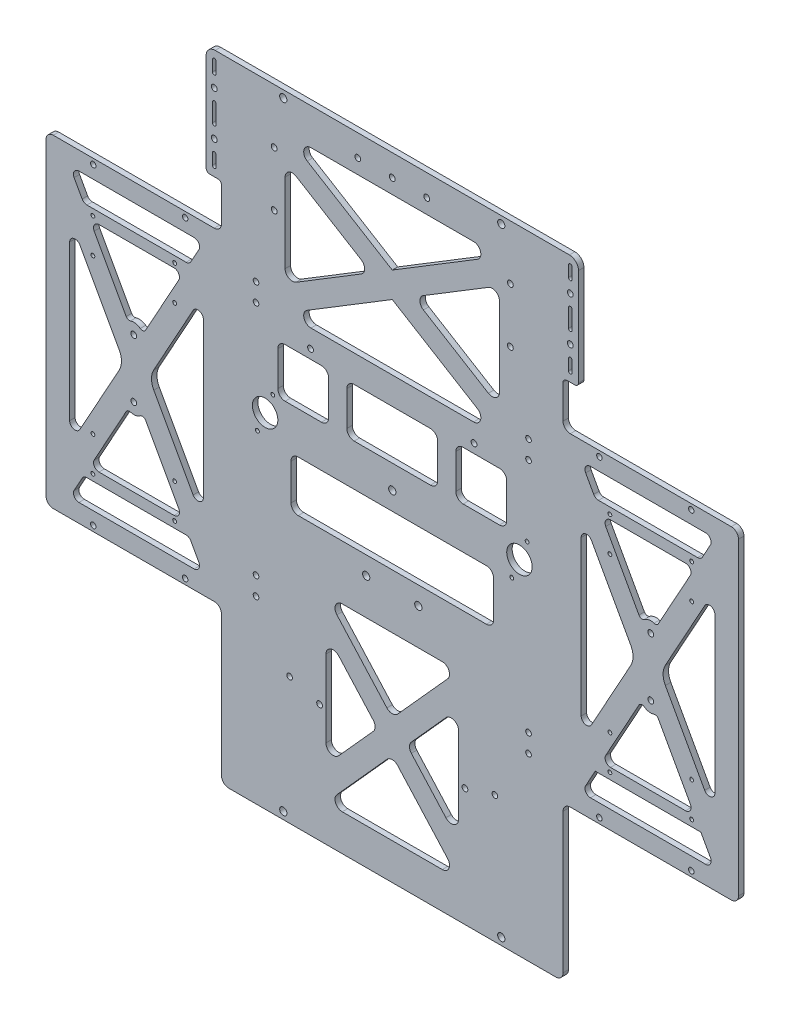
SolidWorks part; units mm, degrees
material "Thornel Mat VMA"
ref_plane "前视基准面" through (0, 0, 0) normal (0, 0, 1) x (1, 0, 0)
ref_plane "上视基准面" through (0, 0, 0) normal (0, 1, 0) x (1, 0, 0)
ref_plane "右视基准面" through (0, 0, 0) normal (1, 0, 0) x (0, 0, -1)
sketch "草图1" plane through (0, 0, 0) normal (0, 0, 1) x (1, 0, 0)
  line L0 (0, 218.8611) -> (0, -216.7734) construction
  line L1 (-286.7115, 0) -> (319.4189, 0) construction
  line L2 (-94, -89) -> (-94, -174)
  line L3 (-94, 174) -> (94, 174)
  line L4 (-94, 174) -> (-94, 89)
  line L5 (-94, -174) -> (94, -174)
  line L6 (94, 174) -> (94, 89)
  line L7 (-94, 174) -> (94, -174) construction
  line L8 (-94, -174) -> (94, 174) construction
  line L9 (-190.6, 89) -> (-94, 89)
  line L10 (-190.6, 89) -> (-190.6, -89)
  line L11 (-190.6, -89) -> (-94, -89)
  line L13 (190.6, 89) -> (94, 89)
  line L14 (190.6, 89) -> (190.6, -89)
  line L15 (190.6, -89) -> (94, -89)
  line L17 (94, -89) -> (94, -174)
  point P5 (0, 0)
  dimension "D1" = 381.2
  dimension "D2" = 188
  dimension "D3" = 178
  dimension "D4" = 348
extrude "凸台-拉伸1" add sketch "草图1" along normal blind 3
sketch "草图2" plane through (0, 0, 3) normal (0, 0, 1) x (1, 0, 0)
  line L0 (0, 167.8944) -> (0, -170.5969) construction
  line L1 (-236.471, 0) -> (218.9046, 0) construction
  line L2 (-190.6, 89) -> (-190.6, -89) construction
  line L3 (190.6, -89) -> (190.6, 89) construction
  line L4 (-177.6, -79) -> (-104, -79)
  line L5 (-177.6, -79) -> (-177.6, 79)
  line L6 (-177.6, 79) -> (-104, 79)
  line L7 (-104, -79) -> (-104, 79)
  line L8 (-177.6, -79) -> (-104, 79) construction
  line L9 (-177.6, 79) -> (-104, -79) construction
  line L10 (104, -79) -> (177.6, -79)
  line L11 (104, -79) -> (104, 79)
  line L12 (104, 79) -> (177.6, 79)
  line L13 (177.6, -79) -> (177.6, 79)
  line L14 (104, -79) -> (177.6, 79) construction
  line L15 (104, 79) -> (177.6, -79) construction
  line L16 (190.6, 89) -> (94, 89) construction
  line L17 (94, 89) -> (94, 174) construction
  circle A0 centre (164.6, 86) radius 1.5
  circle A1 centre (164.6, -86) radius 1.5
  circle A2 centre (-60, -170) radius 1.5
  circle A3 centre (60, -170) radius 1.5
  circle A4 centre (-164.6, -86) radius 1.5
  circle A5 centre (-164.6, 86) radius 1.5
  circle A6 centre (-60, 170) radius 1.5
  circle A7 centre (60, 170) radius 1.5
  circle A8 centre (-114, 86) radius 1.5
  circle A9 centre (-114, -86) radius 1.5
  circle A10 centre (114, 86) radius 1.5
  circle A11 centre (114, -86) radius 1.5
  point P29 (140.8, 0)
  point P33 (-140.8, 0)
  dimension "D1" = 3
  dimension "D2" = 120
  dimension "D3" = 50.6
  dimension "D4" = 172
  dimension "D5" = 26
  dimension "D6" = 340
  dimension "D7" = 13
  dimension "D8" = 10
  dimension "D9" = 10
extrude "切除-拉伸1" cut sketch "草图2" against normal through all
sketch "草图3" plane through (0, 0, 3) normal (0, 0, 1) x (1, 0, 0)
  line L0 (-177.6, 79) -> (-169.8636, 65)
  line L1 (-104, -79) -> (-104, 79) construction
  line L2 (-104, -54.1893) -> (-104, -79)
  line L3 (-104, -79) -> (-111.7364, -65)
  line L4 (-177.6, 79) -> (-177.6, -79) construction
  line L5 (-177.6, 54.1893) -> (-177.6, 79)
  line L6 (-104, 79) -> (-111.7364, 65)
  line L7 (-177.6, -54.1893) -> (-177.6, -79)
  line L8 (-177.6, -79) -> (-169.8636, -65)
  line L9 (-104, 54.1893) -> (-104, 79)
  line L11 (-104, 79) -> (-177.6, 79) construction
  line L14 (-169.8636, 65) -> (-111.7364, 65)
  line L20 (-133.9449, 0) -> (-104, -54.1893)
  line L21 (-147.6551, 0) -> (-177.6, -54.1893)
  line L22 (-147.6551, 0) -> (-177.6, 54.1893)
  line L23 (-133.9449, 0) -> (-104, 54.1893)
  line L28 (-142.3, 12.0792) -> (-142.3, -12.0792) construction
  line L33 (-166.5481, 59) -> (-115.0519, 59)
  line L34 (-164.8, 30) -> (-119.8, 30) construction
  line L35 (-147.6551, 0) -> (-133.9449, 0) construction
  line L36 (-164.8, 30) -> (-164.8, -30) construction
  line L37 (-164.8, -30) -> (-119.8, -30) construction
  line L38 (-119.8, 30) -> (-119.8, -30) construction
  line L39 (-164.8, 30) -> (-119.8, -30) construction
  line L40 (-164.8, -30) -> (-119.8, 30) construction
  line L41 (-166.8, 65) -> (-117.8, 65) construction
  line L42 (-166.8, 65) -> (-166.8, 39) construction
  line L43 (-166.8, 39) -> (-117.8, 39) construction
  line L44 (-117.8, 65) -> (-117.8, 39) construction
  line L45 (-166.8, 65) -> (-117.8, 39) construction
  line L46 (-166.8, 39) -> (-117.8, 65) construction
  line L47 (-164.8, 61.5) -> (-119.8, 61.5) construction
  line L48 (-164.8, 61.5) -> (-164.8, 42.5) construction
  line L49 (-164.8, 42.5) -> (-119.8, 42.5) construction
  line L50 (-119.8, 61.5) -> (-119.8, 42.5) construction
  line L51 (-164.8, 61.5) -> (-119.8, 42.5) construction
  line L52 (-164.8, 42.5) -> (-119.8, 61.5) construction
  line L53 (-115.0519, 59) -> (-137.1305, 19.0457)
  line L54 (-166.5481, 59) -> (-145.5673, 21.0324)
  line L55 (-166.5481, -59) -> (-115.0519, -59)
  line L56 (-169.8636, -65) -> (-111.7364, -65)
  line L57 (-115.0519, -59) -> (-137.1305, -19.0457)
  line L58 (-166.5481, -59) -> (-145.5673, -21.0324)
  line L59 (0, 125.1469) -> (0, -125.1469) construction
  line L60 (164.8, 42.5) -> (119.8, 61.5) construction
  line L61 (164.8, 61.5) -> (119.8, 42.5) construction
  line L62 (119.8, 61.5) -> (119.8, 42.5) construction
  line L63 (164.8, 42.5) -> (119.8, 42.5) construction
  line L64 (164.8, 61.5) -> (164.8, 42.5) construction
  line L65 (164.8, 61.5) -> (119.8, 61.5) construction
  line L66 (166.8, 39) -> (117.8, 65) construction
  line L67 (166.8, 65) -> (117.8, 39) construction
  line L68 (117.8, 65) -> (117.8, 39) construction
  line L69 (166.8, 39) -> (117.8, 39) construction
  line L70 (166.8, 65) -> (166.8, 39) construction
  line L71 (166.8, 65) -> (117.8, 65) construction
  line L72 (164.8, -30) -> (119.8, 30) construction
  line L73 (164.8, 30) -> (119.8, -30) construction
  line L74 (119.8, 30) -> (119.8, -30) construction
  line L75 (164.8, -30) -> (119.8, -30) construction
  line L76 (164.8, 30) -> (164.8, -30) construction
  line L77 (147.6551, 0) -> (133.9449, 0) construction
  line L78 (164.8, 30) -> (119.8, 30) construction
  line L79 (142.3, 12.0792) -> (142.3, -12.0792) construction
  line L80 (166.5481, -59) -> (145.5673, -21.0324)
  line L81 (115.0519, -59) -> (137.1305, -19.0457)
  line L82 (169.8636, -65) -> (111.7364, -65)
  line L83 (166.5481, -59) -> (115.0519, -59)
  line L84 (166.5481, 59) -> (145.5673, 21.0324)
  line L85 (115.0519, 59) -> (137.1305, 19.0457)
  line L86 (166.5481, 59) -> (115.0519, 59)
  line L87 (133.9449, 0) -> (104, 54.1893)
  line L88 (147.6551, 0) -> (177.6, 54.1893)
  line L89 (147.6551, 0) -> (177.6, -54.1893)
  line L90 (133.9449, 0) -> (104, -54.1893)
  line L91 (169.8636, 65) -> (111.7364, 65)
  line L92 (104, 54.1893) -> (104, 79)
  line L93 (177.6, -79) -> (169.8636, -65)
  line L94 (177.6, -54.1893) -> (177.6, -79)
  line L95 (104, 79) -> (111.7364, 65)
  line L96 (177.6, 54.1893) -> (177.6, 79)
  line L97 (104, -79) -> (111.7364, -65)
  line L98 (104, -54.1893) -> (104, -79)
  line L99 (177.6, 79) -> (169.8636, 65)
  circle A0 centre (-142.3, 16) radius 1.6
  circle A1 centre (-164.8, 61.5) radius 1.05
  circle A2 centre (-119.8, 61.5) radius 1.05
  circle A3 centre (-119.8, 42.5) radius 1.05
  circle A4 centre (-164.8, 42.5) radius 1.05
  arc A5 (-137.1305, 19.0457) -> (-145.5673, 21.0324) centre (-142.3, 16) ccw
  arc A6 (-137.1305, -19.0457) -> (-145.5673, -21.0324) centre (-142.3, -16) cw
  circle A7 centre (-142.3, -16) radius 1.6
  circle A8 centre (-119.8, -42.5) radius 1.05
  circle A9 centre (-164.8, -42.5) radius 1.05
  circle A10 centre (-119.8, -61.5) radius 1.05
  circle A11 centre (-164.8, -61.5) radius 1.05
  circle A12 centre (164.8, -61.5) radius 1.05
  circle A13 centre (119.8, -61.5) radius 1.05
  circle A14 centre (164.8, -42.5) radius 1.05
  circle A15 centre (119.8, -42.5) radius 1.05
  circle A16 centre (142.3, -16) radius 1.6
  arc A17 (137.1305, -19.0457) -> (145.5673, -21.0324) centre (142.3, -16) ccw
  arc A18 (137.1305, 19.0457) -> (145.5673, 21.0324) centre (142.3, 16) cw
  circle A19 centre (164.8, 42.5) radius 1.05
  circle A20 centre (119.8, 42.5) radius 1.05
  circle A21 centre (119.8, 61.5) radius 1.05
  circle A22 centre (164.8, 61.5) radius 1.05
  circle A23 centre (142.3, 16) radius 1.6
  point P13 (-142.3, 0)
  point P25 (-142.3, 52)
  point P37 (-142.3, 52)
  point P69 (0, 0)
  point P122 (142.3, 52)
  point P123 (142.3, 0)
  dimension "D4" = 3.2
  dimension "D10" = 2.1
  dimension "D12" = 12
  dimension "D1" = 12
  dimension "D2" = 45
  dimension "D3" = 60
  dimension "D5" = 16
  dimension "D6" = 49
  dimension "D7" = 26
  dimension "D8" = 45
  dimension "D9" = 19
  dimension "D11" = 14
  dimension "D13" = 6
extrude "凸台-拉伸2" add sketch "草图3" against normal up to surface (3 mm away) up to face at (-163.1, -86, 0)
fillet "圆角2" radius 4 10 edges at (-94, -174, 1.5) (-94, -89, 1.5) (-190.6, -89, 1.5) (-190.6, 89, 1.5) (-94, 89, 1.5) (94, -174, 1.5) (94, -89, 1.5) (190.6, -89, 1.5) (190.6, 89, 1.5) (94, 89, 1.5)
sketch "草图4" plane through (0, 0, 3) normal (0, 0, 1) x (1, 0, 0)
  circle A0 centre (-60, 170) radius 2
  circle A1 centre (60, 170) radius 2
  circle A2 centre (-60, -170) radius 2
  circle A3 centre (60, -170) radius 2
  dimension "D1" = 4
extrude "切除-拉伸2" cut sketch "草图4" against normal through all
fillet "圆角3" radius 2 8 edges at (-145.5673, 21.0324, 1.5) (-137.1305, 19.0457, 1.5) (-145.5673, -21.0324, 1.5) (-137.1305, -19.0457, 1.5) (145.5673, -21.0324, 1.5) (137.1305, -19.0457, 1.5) (145.5673, 21.0324, 1.5) (137.1305, 19.0457, 1.5)
fillet "圆角4" radius 3 30 edges at (-169.8636, -65, 1.5) (-111.7364, -65, 1.5) (-169.8636, 65, 1.5) (-111.7364, 65, 1.5) (-177.6, -79, 1.5) (-166.5481, -59, 1.5) (-177.6, -54.1893, 1.5) (-177.6, 54.1893, 1.5) (-104, 54.1893, 1.5) (-104, -79, 1.5) (-115.0519, -59, 1.5) (-104, -54.1893, 1.5) (-177.6, 79, 1.5) (-166.5481, 59, 1.5) (-104, 79, 1.5) (-115.0519, 59, 1.5) (104, -54.1893, 1.5) (115.0519, -59, 1.5) (104, -79, 1.5) (166.5481, -59, 1.5) (177.6, -79, 1.5) (177.6, -54.1893, 1.5) (104, 54.1893, 1.5) (177.6, 54.1893, 1.5) (115.0519, 59, 1.5) (166.5481, 59, 1.5) (111.7364, 65, 1.5) (169.8636, 65, 1.5) (177.6, 79, 1.5) (104, 79, 1.5)
fillet "圆角5" radius 10 4 edges at (147.6551, 0, 1.5) (133.9449, 0, 1.5) (-133.9449, 0, 1.5) (-147.6551, 0, 1.5)
sketch "草图19" plane through (0, 0, 0) normal (0, 0, -1) x (-1, 0, 0)
  line L0 (0, 174) -> (0, -174) construction
  line L1 (-94, 174) -> (-102.5, 174)
  line L2 (-94, 174) -> (-94, 113.5)
  line L3 (-94, 113.5) -> (-102.5, 113.5)
  line L4 (-102.5, 174) -> (-102.5, 113.5)
  line L5 (94, 174) -> (102.5, 174)
  line L6 (94, 174) -> (94, 113.5)
  line L7 (94, 113.5) -> (102.5, 113.5)
  line L8 (102.5, 174) -> (102.5, 113.5)
  line L9 (-94, 174) -> (94, 174) construction
  line L10 (90, -174) -> (-90, -174) construction
  point P16 (102.5, 143.75)
  dimension "D1" = 205
  dimension "D2" = 60.5
extrude "凸台-拉伸3" add sketch "草图19" against normal up to surface (3 mm away) up to face at (62, 170, 3)
sketch "草图20" plane through (0, 0, 0) normal (0, 0, -1) x (-1, 0, 0)
  line L0 (0, 174) -> (0, 0) construction
  line L1 (-102.5, 174) -> (102.5, 174) construction
  line L3 (-99, 169) -> (-97, 169)
  line L4 (-99, 169) -> (-99, 163)
  line L5 (-99, 163) -> (-97, 163)
  line L6 (-97, 169) -> (-97, 163)
  line L7 (-99, 148.75) -> (-97, 148.75)
  line L8 (-99, 148.75) -> (-99, 138.75)
  line L9 (-99, 138.75) -> (-97, 138.75)
  line L10 (-97, 148.75) -> (-97, 138.75)
  line L11 (-99, 124.5) -> (-97, 124.5)
  line L12 (-99, 124.5) -> (-99, 118.5)
  line L13 (-99, 118.5) -> (-97, 118.5)
  line L14 (-97, 124.5) -> (-97, 118.5)
  line L15 (-99, 143.75) -> (-82.4627, 143.75) construction
  line L16 (99, 118.5) -> (97, 118.5)
  line L17 (97, 124.5) -> (97, 118.5)
  line L18 (99, 124.5) -> (97, 124.5)
  line L19 (99, 124.5) -> (99, 118.5)
  line L20 (99, 138.75) -> (97, 138.75)
  line L21 (97, 148.75) -> (97, 138.75)
  line L22 (99, 148.75) -> (97, 148.75)
  line L23 (99, 148.75) -> (99, 138.75)
  line L24 (99, 163) -> (97, 163)
  line L25 (97, 169) -> (97, 163)
  line L26 (99, 169) -> (97, 169)
  line L27 (99, 169) -> (99, 163)
  dimension "D1" = 6
  dimension "D2" = 10
  dimension "D3" = 5
  dimension "D4" = 25.25
  dimension "D5" = 198
  dimension "D6" = 2
extrude "切除-拉伸13" cut sketch "草图20" against normal through all
sketch "草图22" plane through (0, 0, 0) normal (0, 0, -1) x (-1, 0, 0)
  line L0 (-99, 143.75) -> (169.7088, 143.75) construction
  line L1 (-99, 148.75) -> (-99, 138.75) construction
  line L2 (-98, 169) -> (-98, 118.5) construction
  line L3 (-97, 169) -> (-99, 169) construction
  line L4 (-99, 118.5) -> (-97, 118.5) construction
  line L5 (0, 174) -> (0, 199.7438) construction
  line L6 (-102.5, 174) -> (102.5, 174) construction
  line L7 (-99, 163) -> (-97, 163) construction
  line L8 (-97, 148.75) -> (-99, 148.75) construction
  line L9 (-99, 138.75) -> (-97, 138.75) construction
  line L10 (-97, 124.5) -> (-99, 124.5) construction
  circle A0 centre (-98, 155.875) radius 1.6
  circle A1 centre (-98, 131.625) radius 1.6
  circle A2 centre (-98, 169) radius 1
  circle A3 centre (-98, 163) radius 1
  circle A4 centre (-98, 148.75) radius 1
  circle A5 centre (-98, 138.75) radius 1
  circle A6 centre (-98, 124.5) radius 1
  circle A7 centre (-98, 118.5) radius 1
  circle A8 centre (98, 169) radius 1
  circle A9 centre (98, 163) radius 1
  circle A10 centre (98, 155.875) radius 1.6
  circle A11 centre (98, 148.75) radius 1
  circle A12 centre (98, 138.75) radius 1
  circle A13 centre (98, 131.625) radius 1.6
  circle A14 centre (98, 124.5) radius 1
  circle A15 centre (98, 118.5) radius 1
  dimension "D1" = 24.25
  dimension "D2" = 3.2
extrude "切除-拉伸14" cut sketch "草图22" against normal through all
sketch "草图23" plane through (0, 0, 0) normal (0, 0, -1) x (-1, 0, 0)
  line L0 (0, 174) -> (0, -174) construction
  line L1 (-102.5, 174) -> (102.5, 174) construction
  line L2 (90, -174) -> (-90, -174) construction
  line L3 (-177.6, 0) -> (190.6, 0) construction
  line L4 (-177.6, -42.5577) -> (-177.6, 42.5577) construction
  line L5 (190.6, 85) -> (190.6, -85) construction
  line L6 (-74.225, 25.685) -> (-65.775, 4.315) construction
  line L7 (65.775, 25.685) -> (74.225, 4.315) construction
  circle A0 centre (-65, 144) radius 1.6
  circle A1 centre (65, 144) radius 1.6
  circle A2 centre (-65, 114) radius 1.6
  circle A3 centre (65, 114) radius 1.6
  circle A4 centre (0, 13) radius 2
  circle A5 centre (-14.35, -34.9) radius 2
  circle A6 centre (14.35, -34.9) radius 2
  circle A7 centre (-74.225, 25.685) radius 1.05
  circle A8 centre (-65.775, 4.315) radius 1.05
  circle A9 centre (65.775, 25.685) radius 1.05
  circle A10 centre (74.225, 4.315) radius 1.05
  circle A13 centre (-45, 58) radius 1.6
  circle A14 centre (45, 58) radius 1.6
  circle A17 centre (-56.5, -104) radius 1.55
  circle A18 centre (56.5, -104) radius 1.55
  circle A19 centre (-70, 15) radius 7
  circle A20 centre (70, 15) radius 7
  point P30 (-70, 15)
  point P32 (70, 15)
  dimension "D1" = 3.2
  dimension "D2" = 30
  dimension "D3" = 130
  dimension "D4" = 30
  dimension "D5" = 28.7
  dimension "D6" = 4
  dimension "D7" = 47.9
  dimension "D8" = 13
  dimension "D9" = 21.37
  dimension "D10" = 2.1
  dimension "D11" = 8.45
  dimension "D12" = 8.45
  dimension "D16" = 3.2
  dimension "D17" = 90
  dimension "D18" = 116
  dimension "D19" = 113
  dimension "D21" = 3.1
  dimension "D22" = 70
  dimension "D26" = 14
  dimension "D13" = 21.37
  dimension "D14" = 140
  dimension "D15" = 15
extrude "切除-拉伸15" cut sketch "草图23" against normal through all
sketch "草图24" plane through (0, 0, 0) normal (0, 0, -1) x (-1, 0, 0)
  line L0 (-190.6, 0) -> (190.6, 0) construction
  line L1 (-190.6, -85) -> (-190.6, 85) construction
  line L2 (190.6, 85) -> (190.6, -85) construction
  line L3 (0, -174) -> (0, 174) construction
  line L4 (90, -174) -> (-90, -174) construction
  line L5 (-102.5, 174) -> (102.5, 174) construction
  line L6 (-104, 42.5577) -> (-104, -42.5577) construction
  circle A0 centre (-75, 75) radius 1.55
  circle A1 centre (-75, 65) radius 1.55
  circle A2 centre (-75, -65) radius 1.55
  circle A3 centre (-75, -75) radius 1.55
  circle A4 centre (75, -65) radius 1.55
  circle A5 centre (75, -75) radius 1.55
  circle A6 centre (75, 75) radius 1.55
  circle A7 centre (75, 65) radius 1.55
  dimension "D1" = 3.1
  dimension "D2" = 10
  dimension "D3" = 10
  dimension "D4" = 29
  dimension "D5" = 130
  dimension "D6" = 65
extrude "切除-拉伸16" cut sketch "草图24" against normal through all
sketch "草图26" plane through (0, 0, 0) normal (0, 0, -1) x (-1, 0, 0)
  line L0 (0, -174) -> (0, 202.1106) construction
  line L1 (90, -174) -> (-90, -174) construction
  line L2 (-102.5, 174) -> (102.5, 174) construction
  line L3 (-59, 154) -> (59, 154)
  line L4 (-59, 154) -> (-59, 68)
  line L5 (-59, 68) -> (59, 68)
  line L6 (59, 154) -> (59, 68)
  line L7 (-59, 154) -> (59, 68) construction
  line L8 (-59, 68) -> (59, 154) construction
  line L9 (-63, 53) -> (63, 53)
  line L10 (-63, 53) -> (-63, 26)
  line L11 (-63, 26) -> (63, 26)
  line L12 (63, 53) -> (63, 26)
  line L13 (-63, 53) -> (63, 26) construction
  line L14 (-63, 26) -> (63, 53) construction
  line L15 (-55.775, 3) -> (55.775, 3)
  line L16 (-55.775, 3) -> (-55.775, -24.9)
  line L17 (-55.775, -24.9) -> (55.775, -24.9)
  line L18 (55.775, 3) -> (55.775, -24.9)
  line L19 (-55.775, 3) -> (55.775, -24.9) construction
  line L20 (-55.775, -24.9) -> (55.775, 3) construction
  line L21 (-94, -170) -> (-94, -93) construction
  line L26 (-74, -85) -> (-61.5, -85) construction
  line L27 (-36.5, -54.9) -> (36.5, -54.9)
  line L32 (-36.5, -54.9) -> (-36.5, -154)
  line L33 (-36.5, -154) -> (36.5, -154)
  line L34 (-74, -85) -> (-74, -149) construction
  line L35 (36.5, -54.9) -> (36.5, -154)
  line L36 (-36.5, -54.9) -> (36.5, -154) construction
  line L37 (-36.5, -154) -> (36.5, -54.9) construction
  line L38 (-74, -149) -> (-61.5, -149) construction
  line L39 (-61.5, -85) -> (-61.5, -149) construction
  line L40 (61.5, -85) -> (74, -85) construction
  line L41 (61.5, -85) -> (61.5, -149) construction
  line L42 (61.5, -149) -> (74, -149) construction
  line L43 (74, -85) -> (74, -149) construction
  circle A0 centre (-65, 114) radius 1.6 construction
  circle A1 centre (-45, 58) radius 1.6 construction
  circle A2 centre (0, 13) radius 2 construction
  circle A3 centre (-14.35, -34.9) radius 2 construction
  circle A4 centre (-65.775, 4.315) radius 1.05 construction
  circle A5 centre (56.5, -104) radius 1.55 construction
  circle A6 centre (-75, 65) radius 1.55 construction
  circle A7 centre (-56.5, -104) radius 1.55 construction
  circle A8 centre (-75, -75) radius 1.55 construction
  circle A10 centre (14.35, -34.9) radius 2 construction
  point P5 (0, 111)
  point P10 (0, 39.5)
  point P15 (0, -10.95)
  point P26 (0, -104.45)
  dimension "D12" = 20
  dimension "D14" = 5
  dimension "D1" = 20
  dimension "D2" = 6
  dimension "D3" = 10
  dimension "D4" = 10
  dimension "D5" = 10
  dimension "D6" = 10
  dimension "D7" = 5
  dimension "D8" = 13
  dimension "D9" = 12
  dimension "D10" = 20
  dimension "D11" = 20
  dimension "D13" = 20
  dimension "D15" = 10
  dimension "D16" = 25
extrude "切除-拉伸17" cut sketch "草图26" against normal through all
sketch "草图27" plane through (0, 0, 0) normal (0, 0, -1) x (-1, 0, 0)
  line L0 (-59, 154) -> (0, 118.0273)
  line L1 (59, 68) -> (59, 154) construction
  line L2 (59, 82.0546) -> (59, 68)
  line L3 (59, 68) -> (0, 103.9727)
  line L4 (-59, 154) -> (-59, 68) construction
  line L5 (-59, 139.9454) -> (-59, 154)
  line L6 (59, 154) -> (0, 118.0273)
  line L7 (-59, 82.0546) -> (-59, 68)
  line L8 (-59, 68) -> (0, 103.9727)
  line L9 (59, 139.9454) -> (59, 154)
  line L10 (-11.5257, 111) -> (-59, 82.0546)
  line L11 (11.5257, 111) -> (59, 82.0546)
  line L12 (11.5257, 111) -> (59, 139.9454)
  line L13 (-11.5257, 111) -> (-59, 139.9454)
  line L14 (0, 0) -> (0, 96.1037) construction
  line L15 (63, 53) -> (-63, 53) construction
  line L16 (-35, 53) -> (-25, 53)
  line L17 (-35, 53) -> (-35, 26)
  line L18 (-35, 26) -> (-25, 26)
  line L19 (-25, 53) -> (-25, 26)
  line L20 (-63, 26) -> (63, 26) construction
  line L21 (-36.5, -54.9) -> (0, -95.4782)
  line L22 (25, 53) -> (35, 53)
  line L23 (25, 53) -> (25, 26)
  line L24 (25, 26) -> (35, 26)
  line L25 (35, 53) -> (35, 26)
  line L26 (36.5, -154) -> (36.5, -54.9) construction
  line L27 (36.5, -136.0563) -> (36.5, -154)
  line L28 (36.5, -154) -> (0, -113.4218)
  line L29 (-36.5, -54.9) -> (-36.5, -154) construction
  line L30 (-36.5, -72.8437) -> (-36.5, -54.9)
  line L31 (36.5, -54.9) -> (0, -95.4782)
  line L32 (-36.5, -136.0563) -> (-36.5, -154)
  line L33 (-36.5, -154) -> (0, -113.4218)
  line L34 (36.5, -72.8437) -> (36.5, -54.9)
  line L35 (8.0702, -104.45) -> (36.5, -72.8437)
  line L36 (8.0702, -104.45) -> (36.5, -136.0563)
  line L37 (-8.0702, -104.45) -> (-36.5, -136.0563)
  line L38 (-8.0702, -104.45) -> (-36.5, -72.8437)
  dimension "D1" = 12
  dimension "D2" = 10
  dimension "D3" = 50
  dimension "D4" = 12
extrude "凸台-拉伸4" add sketch "草图27" against normal up to surface (3 mm away) up to face at (0, 111, 3)
fillet "圆角6" radius 4 38 edges at (55.775, -24.9, 1.5) (55.775, 3, 1.5) (-55.775, -24.9, 1.5) (-55.775, 3, 1.5) (63, 53, 1.5) (63, 26, 1.5) (35, 26, 1.5) (35, 53, 1.5) (25, 53, 1.5) (25, 26, 1.5) (-25, 26, 1.5) (-25, 53, 1.5) (-35, 53, 1.5) (-35, 26, 1.5) (-63, 26, 1.5) (-63, 53, 1.5) (-59, 68, 1.5) (59, 68, 1.5) (59, 82.0546, 1.5) (-11.5257, 111, 1.5) (11.5257, 111, 1.5) (59, 139.9454, 1.5) (59, 154, 1.5) (-59, 154, 1.5) (-59, 139.9454, 1.5) (-59, 82.0546, 1.5) (36.5, -154, 1.5) (36.5, -136.0563, 1.5) (36.5, -72.8437, 1.5) (8.0702, -104.45, 1.5) (0, -113.4218, 1.5) (-36.5, -154, 1.5) (-36.5, -136.0563, 1.5) (-36.5, -72.8437, 1.5) (-8.0702, -104.45, 1.5) (0, -95.4782, 1.5) (-36.5, -54.9, 1.5) (36.5, -54.9, 1.5)
fillet "圆角7" radius 2 4 edges at (94, 113.5, 1.5) (102.5, 113.5, 1.5) (-102.5, 113.5, 1.5) (-94, 113.5, 1.5)
fillet "圆角8" radius 5 2 edges at (102.5, 174, 1.5) (-102.5, 174, 1.5)
sketch "草图29" plane through (0, 0, 0) normal (0, 0, -1) x (-1, 0, 0)
  line L0 (0, -174) -> (0, -127.1261) construction
  line L1 (90, -174) -> (-90, -174) construction
  line L2 (0, 174) -> (0, 144.3468) construction
  line L3 (44.7557, 154) -> (-44.7557, 154) construction
  line L5 (-97.5, 174) -> (97.5, 174) construction
  circle A0 centre (-19, 162) radius 1.6
  circle A1 centre (19, 162) radius 1.6
  circle A2 centre (0, 162) radius 1.6
  dimension "D1" = 3.2
  dimension "D2" = 8
  dimension "D4" = 38
extrude "切除-拉伸18" cut sketch "草图29" against normal through all
sketch "草图30" plane through (0, 0, 0) normal (0, 0, -1) x (-1, 0, 0)
  line L0 (0, -174) -> (0, 0) construction
  line L1 (90, -174) -> (-90, -174) construction
  line L2 (36.5, -125.6282) -> (36.5, -83.2718) construction
  circle A0 centre (-40, -109) radius 1.6
  circle A1 centre (40, -109) radius 1.6
  dimension "D1" = 80
  dimension "D2" = 3.2
  dimension "D3" = 3.5
  dimension "D4" = 65
extrude "切除-拉伸19" cut sketch "草图30" against normal through all
